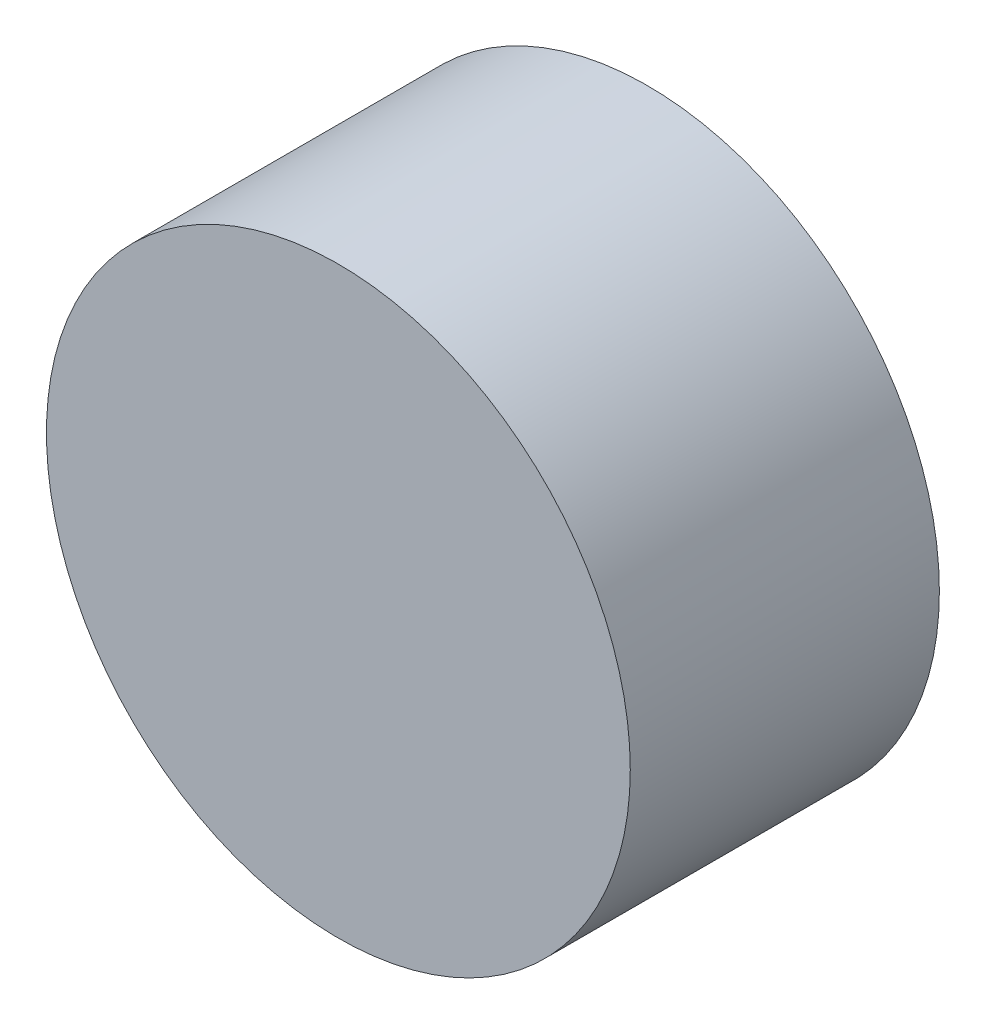
SolidWorks part; units mm, degrees
ref_plane "Front Plane" through (0, 0, 0) normal (0, 0, 1) x (1, 0, 0)
ref_plane "Top Plane" through (0, 0, 0) normal (0, 1, 0) x (1, 0, 0)
ref_plane "Right Plane" through (0, 0, 0) normal (1, 0, 0) x (0, 0, -1)
sketch "Sketch1" plane through (0, 0, 0) normal (0, 0, 1) x (1, 0, 0)
  circle A0 centre (0, 0) radius 8.5
extrude "Boss-Extrude1" add sketch "Sketch1" along normal blind 4.5 and the other way blind 4.5
